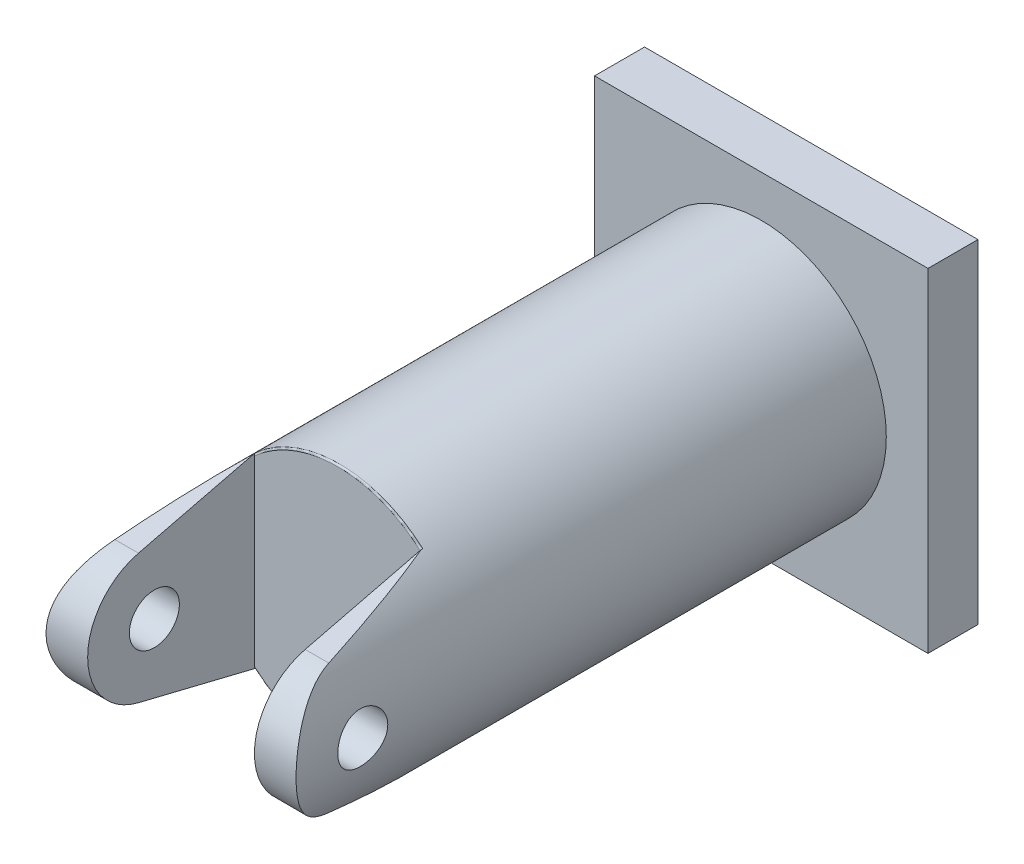
SolidWorks part; units mm, degrees
material "Alloy Steel"
ref_plane "Ön Düzlem" through (0, 0, 0) normal (0, 0, 1) x (1, 0, 0)
ref_plane "Üst Düzlem" through (0, 0, 0) normal (0, 1, 0) x (1, 0, 0)
ref_plane "Sağ Düzlem" through (0, 0, 0) normal (1, 0, 0) x (0, 0, -1)
sketch "Sketch1" plane through (0, 0, 0) normal (0, 0, 1) x (1, 0, 0)
  circle A0 centre (0, 0) radius 7.5
  dimension "D1" = 15
extrude "Boss-Extrude1" add sketch "Sketch1" along normal blind 35.4
sketch "Sketch3" plane through (0, 0, 35.4) normal (0, 0, 1) x (1, 0, 0)
  line L1 (5, 8) -> (-5, 8)
  line L2 (5, 8) -> (5, -8)
  line L3 (5, -8) -> (-5, -8)
  line L4 (-5, 8) -> (-5, -8)
  line L5 (5, 8) -> (-5, -8) construction
  line L6 (5, -8) -> (-5, 8) construction
  point P0 (0, 0)
  dimension "D1" = 16
  dimension "D2" = 10
extrude "Cut-Extrude2" cut sketch "Sketch3" against normal blind 10
sketch "Sketch4" plane through (0, 0, 0) normal (1, 0, 0) x (0, 0, -1)
  line L0 (-25.4, 7.5) -> (-25.4, 5.5902)
  line L1 (-25.4, 5.5902) -> (-32.3529, 3.8847)
  line L2 (-25.4, -7.5) -> (-25.4, -5.5902)
  line L3 (-25.4, -5.5902) -> (-32.3527, -3.885)
  line L4 (-35.4, 5.5902) -> (-35.4, -5.5902) construction
  line L5 (-35.4, -5.5902) -> (-25.4, -5.5902) construction
  arc A0 (-32.3529, 3.8847) -> (-32.3527, -3.885) centre (-31.4, -0.0002) ccw
  dimension "D1" = 4
  dimension "D2" = 5.59
extrude "Cut-Extrude3" cut sketch "Sketch4" against normal through all both and the other way through all
sketch "Sketch5" plane through (0, 0, 0) normal (1, 0, 0) x (0, 0, -1)
  circle A0 centre (-31.4, -0.0002) radius 1.5
  arc A1 (-32.3529, 3.8847) -> (-32.3527, -3.885) centre (-31.4, -0.0002) ccw construction
  dimension "D1" = 3
extrude "Cut-Extrude4" cut sketch "Sketch5" against normal through all both and the other way through all
fillet "Fillet1" radius 0.1 2 edges at (0, -7.5, 25.4) (0, 7.5, 25.4)
sketch "Sketch6" plane through (0, 0, 0) normal (0, 0, -1) x (-1, 0, 0)
  line L1 (10, 10) -> (-10, 10)
  line L2 (10, 10) -> (10, -10)
  line L3 (10, -10) -> (-10, -10)
  line L4 (-10, 10) -> (-10, -10)
  line L5 (10, 10) -> (-10, -10) construction
  line L6 (10, -10) -> (-10, 10) construction
  point P0 (0, 0)
  dimension "D1" = 20
  dimension "D2" = 20
extrude "Boss-Extrude2" add sketch "Sketch6" along normal blind 3
